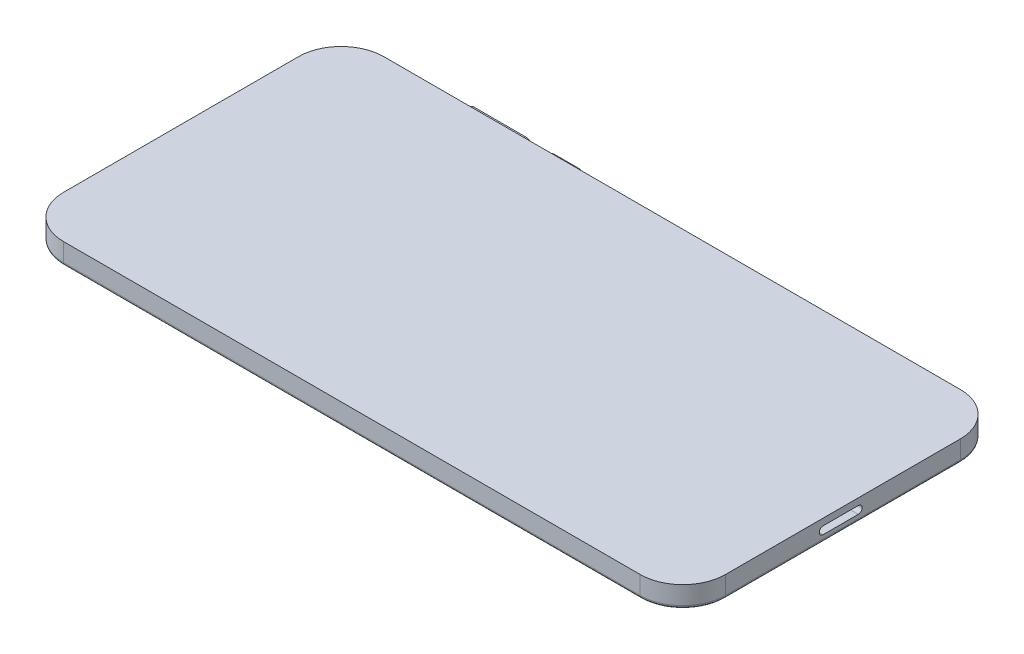
SolidWorks part; units mm, degrees
ref_plane "前视基准面" through (0, 0, 0) normal (0, 0, 1) x (1, 0, 0)
ref_plane "上视基准面" through (0, 0, 0) normal (0, 1, 0) x (1, 0, 0)
ref_plane "右视基准面" through (0, 0, 0) normal (1, 0, 0) x (0, 0, -1)
other "Configuration Table"
sketch "草图1" plane through (0, 0, 0) normal (0, 1, 0) x (1, 0, 0)
  line L1 (-50.4122, 246.4643) -> (489.5878, 246.4643)
  line L2 (-90.4122, 206.4643) -> (-90.4122, -13.5357)
  line L3 (-50.4122, -53.5357) -> (489.5878, -53.5357)
  line L4 (529.5878, 206.4643) -> (529.5878, -13.5357)
  arc A0 (529.5878, 206.4643) -> (489.5878, 246.4643) centre (489.5878, 206.4643) ccw
  arc A1 (489.5878, -53.5357) -> (529.5878, -13.5357) centre (489.5878, -13.5357) ccw
  arc A2 (-50.4122, 246.4643) -> (-90.4122, 206.4643) centre (-50.4122, 206.4643) ccw
  arc A3 (-90.4122, -13.5357) -> (-50.4122, -53.5357) centre (-50.4122, -13.5357) ccw
  point P4 (219.5878, 246.4643)
  dimension "D1" = 40
  dimension "D2" = 40
  dimension "D3" = 40
extrude "凸台-拉伸1" add sketch "草图1" along normal blind 20
sketch "草图3" plane through (529.5878, 0, 0) normal (1, 0, 0) x (0, 0, -1)
  line L2 (77.8205, 13.7404) -> (110.8949, 13.7404)
  line L3 (77.8205, 13.7404) -> (77.8205, 6.5778)
  line L4 (77.8205, 6.5778) -> (110.8949, 6.5778)
  line L5 (110.8949, 13.7404) -> (110.8949, 6.5778)
  arc A0 (110.8949, 6.5778) -> (110.8949, 13.7404) centre (110.8949, 10.1591) ccw
  arc A1 (77.8205, 13.7404) -> (77.8205, 6.5778) centre (77.8205, 10.1591) ccw
extrude "切除-拉伸1" cut sketch "草图3" against normal blind 50 contours L3 A1 | L5 L2 L3 L4 | L5 A0 region at (529.5878, 10.1591, -94.3577) region at (529.5878, 10.1591, -76.3006) region at (529.5878, 10.1591, -112.4148)
sketch "草图6" plane through (529.5878, 0, 0) normal (1, 0, 0) x (0, 0, -1)
  line L0 (47.6955, 10.1591) -> (3.0346, 10.1591) construction
  line L1 (47.6955, 6.2997) -> (3.0346, 6.2997)
  line L2 (47.6955, 14.0185) -> (3.0346, 14.0185)
  arc A0 (47.6955, 6.2997) -> (47.6955, 14.0185) centre (47.6955, 10.1591) ccw
  arc A1 (3.0346, 14.0185) -> (3.0346, 6.2997) centre (3.0346, 10.1591) ccw
  circle A2 centre (3.0346, 10.1591) radius 2.1066
  circle A3 centre (143.3372, 10.1591) radius 3
  circle A4 centre (153.6598, 10.1591) radius 3
  circle A5 centre (165.6676, 10.1591) radius 3
  circle A6 centre (177.6755, 10.1591) radius 3
  point P3 (25.365, 10.1591)
sketch "草图7" plane through (0, 0, -246.4643) normal (0, 0, -1) x (-1, 0, 0)
  line L0 (-29.1119, 10.2288) -> (-77.4384, 10.2288) construction
  line L1 (-29.1119, 4.1336) -> (-77.4384, 4.1336)
  line L2 (-29.1119, 16.3241) -> (-77.4384, 16.3241)
  line L3 (-126.9795, 10.2288) -> (-104.6039, 10.2288) construction
  line L4 (-126.9795, 15.6774) -> (-104.6039, 15.6774)
  line L5 (-126.9795, 4.7803) -> (-104.6039, 4.7803)
  arc A0 (-29.1119, 4.1336) -> (-29.1119, 16.3241) centre (-29.1119, 10.2288) ccw
  arc A1 (-77.4384, 16.3241) -> (-77.4384, 4.1336) centre (-77.4384, 10.2288) ccw
  arc A2 (-126.9795, 15.6774) -> (-126.9795, 4.7803) centre (-126.9795, 10.2288) ccw
  arc A3 (-104.6039, 4.7803) -> (-104.6039, 15.6774) centre (-104.6039, 10.2288) ccw
  point P2 (-53.2752, 10.2288)
  point P7 (-115.7917, 10.2288)
extrude "凸台-拉伸3" add sketch "草图7" along normal blind 5
sketch "草图8" plane through (0, 0, 0) normal (0, -1, 0) x (1, 0, 0)
  line L1 (89.6424, -218.9097) -> (-49.2825, -218.9097)
  line L2 (109.6424, -198.9097) -> (109.6424, -102.6378)
  line L3 (89.6424, -82.6378) -> (-49.2825, -82.6378)
  line L4 (-69.2825, -198.9097) -> (-69.2825, -102.6378)
  arc A0 (109.6424, -102.6378) -> (89.6424, -82.6378) centre (89.6424, -102.6378) ccw
  arc A1 (-49.2825, -82.6378) -> (-69.2825, -102.6378) centre (-49.2825, -102.6378) ccw
  arc A2 (-49.2825, -218.9097) -> (-69.2825, -198.9097) centre (-49.2825, -198.9097) cw
  arc A3 (89.6424, -218.9097) -> (109.6424, -198.9097) centre (89.6424, -198.9097) ccw
  dimension "D1" = 20
  dimension "D2" = 20
extrude "凸台-拉伸4" add sketch "草图8" along normal blind 8 contours L2 A0 L3 A1 L4 A2 L1 A3
sketch "草图9" plane through (0, -8, 0) normal (0, -1, 0) x (-1, 0, 0)
  line L0 (-75.6969, 218.9097) -> (-75.6969, 82.6378)
  line L1 (-89.6424, 218.9097) -> (49.2825, 218.9097) construction
  line L2 (-89.6424, 82.6378) -> (49.2825, 82.6378) construction
  circle A0 centre (24.439, 171.0186) radius 25
  circle A1 centre (-39.9963, 171.0186) radius 25
  circle A2 centre (-9.9555, 112.2432) radius 12.268
  circle A3 centre (-9.9555, 112.2432) radius 19.4948
fillet "圆角2" radius 3 3 edges at (529.5878, 0, -96.4643) (529.5878, 10, -206.4643) (529.5878, 10, 13.5357) type face fillet first side face at (513.7299, 10, 37.6778) first side face at (513.7299, 10, -230.6065) first side face at (-74.5543, 10, -230.6065) first side face at (219.5878, 10, 53.5357) first side face at (219.5878, 0, -96.4643) second side face at (529.5878, 10.1591, -94.3577)
